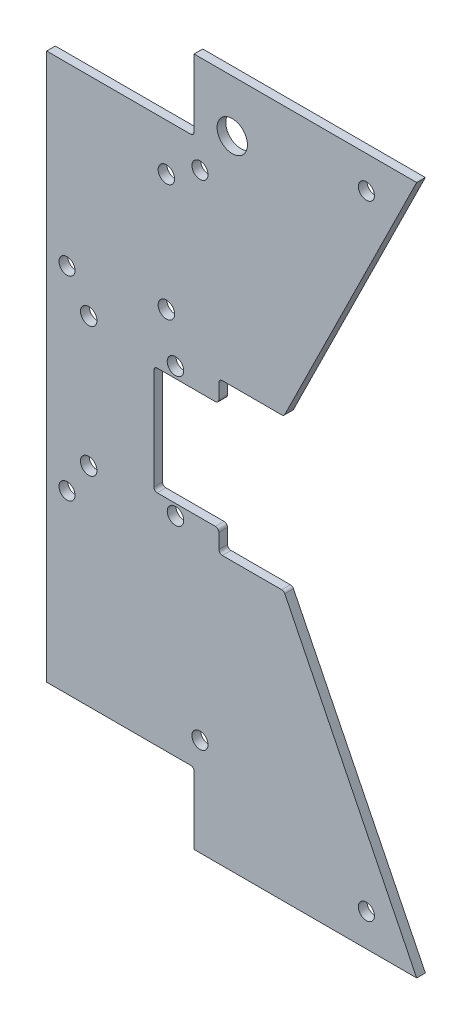
SolidWorks part; units mm, degrees
material "Thornel Mat VMA"
ref_plane "Front Plane" through (0, 0, 0) normal (0, 0, 1) x (1, 0, 0)
ref_plane "Top Plane" through (0, 0, 0) normal (0, 1, 0) x (1, 0, 0)
ref_plane "Right Plane" through (0, 0, 0) normal (1, 0, 0) x (0, 0, -1)
sketch "Sketch1" plane through (0, 0, 0) normal (0, 0, 1) x (1, 0, 0)
  line L0 (-2.9301, -104.5098) -> (-3.3149, -104.5098)
  line L1 (-3.3149, -72.8868) -> (-2.9301, -72.8868)
  line L78 (47.4851, -66.5368) -> (47.4851, -72.8868)
  line L79 (47.4851, -104.5098) -> (47.4851, -110.8598)
  line L80 (66.5174, -66.5368) -> (105.3971, 12.1397)
  line L81 (105.3971, 12.1397) -> (38.7094, 12.1397)
  line L88 (38.7094, 12.1397) -> (38.7094, -8.6883)
  line L89 (-2.9301, -8.6883) -> (38.7094, -8.6883)
  line L90 (-3.3149, -53.8368) -> (-2.9301, -53.8368)
  line L91 (-2.9301, -53.8368) -> (-2.9301, -8.6883)
  line L92 (-3.3149, -66.5368) -> (-3.3149, -53.8368)
  line L93 (-3.3149, -72.8868) -> (-3.3149, -66.5368)
  line L94 (-2.9301, -104.5098) -> (-2.9301, -72.8868)
  line L95 (-3.3149, -110.8598) -> (-3.3149, -104.5098)
  line L96 (66.5174, -110.8598) -> (105.3971, -189.5363)
  line L97 (105.3971, -189.5363) -> (38.7094, -189.5363)
  line L98 (38.7094, -189.5363) -> (38.7094, -168.7083)
  line L99 (-2.9301, -168.7083) -> (38.7094, -168.7083)
  line L106 (-3.3149, -110.8598) -> (-3.3149, -123.5598)
  line L107 (-3.3149, -123.5598) -> (-2.9301, -123.5598)
  line L108 (66.5174, -110.8598) -> (47.4851, -110.8598)
  line L109 (47.4851, -66.5368) -> (66.5174, -66.5368)
  line L110 (47.4851, -104.5098) -> (47.4851, -72.8868)
  line L111 (-2.9301, -123.5598) -> (-2.9301, -168.7083)
  circle A0 centre (90.6739, 2.6147) radius 2.3495
  circle A1 centre (41.9566, -16.4353) radius 2.3495
  circle A2 centre (3.0351, -60.1868) radius 2.3495
  circle A3 centre (3.0351, -117.2098) radius 2.3495
  circle A4 centre (41.9566, -160.9613) radius 2.3495
  circle A5 centre (90.6739, -180.0113) radius 2.3495
  circle A6 centre (51.4094, -3.1003) radius 4.445
  point P2 (90.6739, 2.6147)
  point P4 (41.9566, -16.4353)
  point P6 (3.0351, -60.1868)
  point P8 (3.0351, -117.2098)
  point P10 (41.9566, -160.9613)
  point P11 (90.6739, -180.0113)
  dimension "D2" = 4.699
  dimension "D5" = 8.89
  dimension "D1" = 66.6876
  dimension "D3" = 12.7
  dimension "D4" = 15.24
extrude "Boss-Extrude1" add sketch "Sketch1" along normal blind 2.54
sketch "Sketch2" plane through (0, 0, 2.54) normal (0, 0, 1) x (1, 0, 0)
  line L0 (-3.3149, -53.8368) -> (-3.3149, -72.8868) construction
  line L1 (47.4851, -66.5368) -> (66.5174, -66.5368) construction
  line L2 (47.4851, -88.6983) -> (-2.9301, -88.6983) construction
  line L3 (47.4851, -110.8598) -> (47.4851, -66.5368) construction
  line L4 (-2.9301, -72.8868) -> (-2.9301, -104.5098) construction
  circle A0 centre (9.3851, -69.7118) radius 2.413
  circle A2 centre (34.7851, -69.7118) radius 2.413
  circle A4 centre (34.7851, -107.6848) radius 2.413
  circle A6 centre (9.3851, -107.6848) radius 2.413
  dimension "D1" = 4.826
  dimension "D2" = 25.4
  dimension "D3" = 4.826
  dimension "D5" = 12.7
  dimension "D7" = 3.175
extrude "Cut-Extrude1" cut sketch "Sketch2" against normal through all
sketch "Sketch3" plane through (0, 0, 2.54) normal (0, 0, 1) x (1, 0, 0)
  line L0 (47.4851, -110.8598) -> (47.4851, -66.5368) construction
  line L1 (47.4851, -72.8868) -> (28.4351, -72.8868)
  line L2 (47.4851, -72.8868) -> (47.4851, -104.5098)
  line L3 (47.4851, -104.5098) -> (28.4351, -104.5098)
  line L4 (28.4351, -72.8868) -> (28.4351, -104.5098)
  line L5 (47.4851, -66.5368) -> (66.5174, -66.5368) construction
  line L6 (66.5174, -110.8598) -> (47.4851, -110.8598) construction
  circle A1 centre (9.3851, -69.7118) radius 2.413 construction
  dimension "D3" = 19.05
  dimension "D1" = 6.35
  dimension "D2" = 6.35
extrude "Cut-Extrude2" cut sketch "Sketch3" against normal through all
sketch "Sketch4" plane through (0, 0, 2.54) normal (0, 0, 1) x (1, 0, 0)
  line L0 (-2.9301, -168.7083) -> (38.7094, -168.7083) construction
  line L1 (27.4577, 15.7469) -> (40.2334, 15.7469)
  line L2 (27.4577, 15.7469) -> (27.4577, -8.6883)
  line L3 (27.4577, -8.6883) -> (40.2334, -8.6883)
  line L4 (40.2334, 15.7469) -> (40.2334, -8.6883)
  line L5 (0, -197.042) -> (40.2334, -197.042)
  line L6 (0, -197.042) -> (0, -168.7083)
  line L7 (0, -168.7083) -> (40.2334, -168.7083)
  line L8 (40.2334, -197.042) -> (40.2334, -168.7083)
  line L9 (38.7094, -168.7083) -> (38.7094, -189.5363) construction
  line L10 (38.7094, -8.6883) -> (-2.9301, -8.6883) construction
  dimension "D1" = 1.524
extrude "Cut-Extrude3" cut sketch "Sketch4" against normal through all
sketch "Sketch5" plane through (0, 0, 0) normal (0, 0, -1) x (-1, 0, 0)
  line L0 (2.9301, -8.6883) -> (2.9301, -53.8368) construction
  line L1 (-40.2334, -8.6883) -> (2.9301, -8.6883) construction
  circle A0 centre (-32.1219, -22.4043) radius 2.413
  circle A1 centre (-32.1219, -56.6943) radius 2.413
  dimension "D4" = 4.826
  dimension "D1" = 35.052
  dimension "D2" = 13.716
  dimension "D3" = 34.29
extrude "Cut-Extrude4" cut sketch "Sketch5" against normal through all
sketch "Sketch6" plane through (0, 0, 0) normal (0, 0, -1) x (-1, 0, 0)
  line L0 (2.9301, -8.6883) -> (2.9301, -168.7083)
  line L1 (2.9301, -168.7083) -> (12.6383, -168.7083)
  line L2 (12.6383, -168.7083) -> (12.6383, -8.6883)
  line L3 (12.6383, -8.6883) -> (2.9301, -8.6883)
extrude "Cut-Extrude5" cut sketch "Sketch6" against normal through all
fillet "Fillet1" radius 1 8 edges at (66.5174, -66.5368, 1.27) (47.4851, -66.5368, 1.27) (28.4351, -72.8868, 1.27) (66.5174, -110.8598, 1.27) (28.4351, -104.5098, 1.27) (47.4851, -110.8598, 1.27) (40.2334, -168.7083, 1.27) (40.2334, -8.6883, 1.27)
fillet "Fillet2" radius 1 2 edges at (47.4851, -104.5098, 1.27) (47.4851, -72.8868, 1.27)
